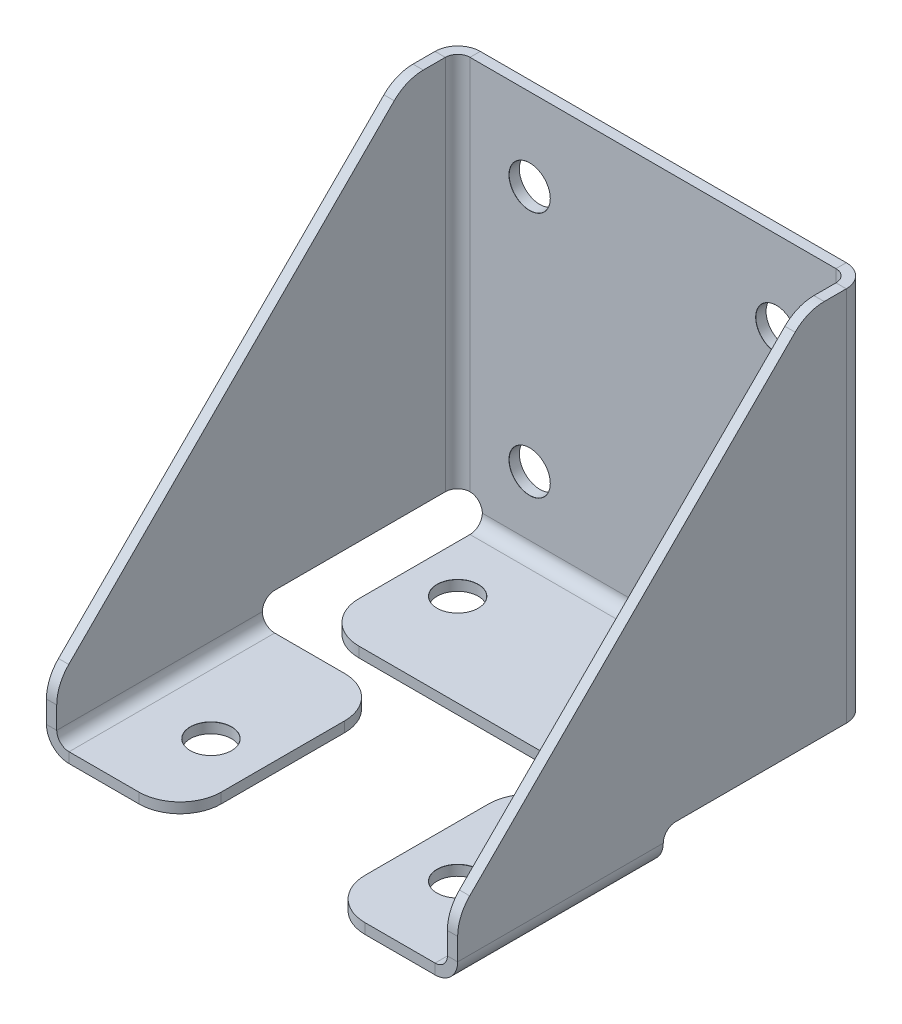
SolidWorks part; units mm, degrees
note: The reader was unsure of these and kept them because the rebuilt part matched: flange length of "Edge-Flange1", "Edge-Flange2", "Edge-Flange3".
ref_plane "Front Plane" through (0, 0, 0) normal (0, 0, 1) x (1, 0, 0)
ref_plane "Top Plane" through (0, 0, 0) normal (0, 1, 0) x (1, 0, 0)
ref_plane "Right Plane" through (0, 0, 0) normal (1, 0, 0) x (0, 0, -1)
sketch "Sketch1" plane through (0, 0, 0) normal (0, 0, 1) x (1, 0, 0)
  line L1 (50, -50) -> (-50, -50)
  line L2 (50, -50) -> (50, 50)
  line L3 (50, 50) -> (-50, 50)
  line L4 (-50, -50) -> (-50, 50)
  line L5 (50, -50) -> (-50, 50) construction
  line L6 (50, 50) -> (-50, -50) construction
  point P0 (0, 0)
  dimension "D1" = 100
  dimension "D2" = 100
base flange "Base-Flange1" sketch "Sketch1" thickness 2.5 reverse thickness direction no parameters "D1"=0.7366
edge flange "Edge-Flange1" sketch "Sketch10" flange angle 90 flange length 42.5 flange position material inside bend radius 3 thickness 2.5 relief rectangular parameters "D6"=10
sketch "Sketch10" plane through (0, -50, 0) normal (0, 1, 0) x (-1, 0, 0)
  line L0 (50, 0) -> (-50, 0) construction
  line L1 (41.5, 0) -> (-41.5, 0)
  line L2 (41.5, 0) -> (41.5, 40)
  line L3 (41.5, 40) -> (-41.5, 40)
  line L4 (-41.5, 40) -> (-41.5, 0)
  line L6 (-50, -2.5) -> (-50, 0) construction
  line L7 (50, -2.5) -> (50, 0) construction
  dimension "D1" = 8.5
  dimension "D2" = 8.5
  dimension "D3" = 40
bend "EdgeBend1" bend radius 3 bend angle 90 parameters "D5"=1
edge flange "Edge-Flange2" sketch "Sketch13" flange angle 90 flange length 100 flange position material inside bend radius 3 thickness 2.5 relief rectangular parameters "D6"=10
sketch "Sketch13" plane through (50, 0, 0) normal (1, 0, 0) x (0, 1, 0)
  line L0 (-50, 0) -> (50, 0) construction
  line L1 (-50, 0) -> (50, 0)
  line L2 (-50, 0) -> (-50, 97.5)
  line L3 (-50, 97.5) -> (50, 97.5)
  line L4 (50, 97.5) -> (50, 0)
bend "EdgeBend2" bend radius 3 bend angle 90 parameters "D5"=2
edge flange "Edge-Flange3" sketch "Sketch16" flange angle 90 flange length 32.5 flange position material inside bend radius 3 thickness 2.5 relief rectangular parameters "D6"=10
sketch "Sketch16" plane through (47.5, -50, 0) normal (0, -1, 0) x (0, 0, 1)
  line L2 (47.5, 0) -> (47.5, 30)
  line L3 (47.5, 30) -> (97.5, 30)
  line L4 (97.5, 30) -> (97.5, 0)
  line L7 (97.5, 0) -> (3, 0) construction
  line L8 (97.5, 0) -> (47.5, 0)
  line L9 (97.5, -2.5) -> (97.5, 0) construction
  dimension "D1" = 30
  dimension "D2" = 50
bend "EdgeBend3" bend radius 3 bend angle 90 parameters "D5"=3
sketch "Sketch17" plane through (50, 0, 0) normal (1, 0, 0) x (0, 0, -1)
  line L0 (-47.5, -50) -> (-47.5, -44.5) construction
  line L1 (-47.5, -41.5) -> (2.5, -41.5)
  line L2 (-47.5, -41.5) -> (-47.5, -50)
  line L3 (-47.5, -50) -> (2.5, -50)
  line L4 (2.5, -41.5) -> (2.5, -50)
  dimension "D1" = 8.5
extrude "Cut-Extrude1" cut sketch "Sketch17" against normal blind 8.5 normal cut yes
sketch "Sketch18" plane through (50, 0, 0) normal (1, 0, 0) x (0, 0, -1)
  line L0 (-97.5, 50) -> (-97.5, -35)
  line L1 (-97.5, 50) -> (-97.5, -44.5) construction
  line L2 (-97.5, -35) -> (-12.5, 50)
  line L3 (-3, 50) -> (-97.5, 50) construction
  line L4 (-12.5, 50) -> (-97.5, 50)
  line L5 (2.5, 50) -> (2.5, -41.5) construction
  dimension "D1" = 45
  dimension "D2" = 15
extrude "Cut-Extrude2" cut sketch "Sketch18" against normal up to next normal cut yes
hole_wizard "Ø10.0mm Dowel Hole1" positions "Sketch19" profile "Sketch20" hole size "Ø10.0" standard "ISO" end condition up to next
sketch "Sketch19" plane through (0, 0, 0) normal (0, 0, 1) x (1, 0, 0)
  line L0 (44.5, 50) -> (-50, 50) construction
  line L1 (44.5, -50) -> (17.5, -50) construction
  line L2 (50, -35) -> (50, 50) construction
  point P0 (30, 30)
  point P2 (30, -30)
  dimension "D1" = 20
  dimension "D2" = 20
  dimension "D3" = 20
  dimension "D4" = 20
sketch "Sketch20" plane through (30, 30, 0) normal (1, 0, 0) x (0, -1, 0)
  line L0 (0, 0) -> (0, 2.5)
  line L1 (0, 2.5) -> (5, 2.5)
  line L2 (5, 2.5) -> (5, 0.025)
  line L3 (5, 0.025) -> (5.025, 0)
  line L5 (5.025, 0) -> (0, 0)
  line L6 (-5, 0.025) -> (-5.025, 0) construction
  line L11 (0, -6.35) -> (0, 107.95) construction
  dimension "Thru Hole Dia." = 10
  dimension "Thru Hole Depth" = 2.5
  dimension "Near C'Sink Dia." = 10.05
  dimension "Near C'Sink Angle" = 90
hole_wizard "Ø10.0mm Dowel Hole2" positions "Sketch21" profile "Sketch22" hole size "Ø10.0" standard "ISO" end condition up to next
sketch "Sketch21" plane through (0, -47.5, 0) normal (0, 1, 0) x (1, 0, 0)
  line L0 (50, -97.5) -> (50, -12.5) construction
  line L1 (44.5, -97.5) -> (17.5, -97.5) construction
  line L2 (44.5, 2.5) -> (-50, 2.5) construction
  point P0 (30, -17.5)
  point P2 (30, -77.5)
  dimension "D1" = 20
  dimension "D2" = 20
  dimension "D3" = 20
  dimension "D4" = 20
sketch "Sketch22" plane through (30, -47.5, 17.5) normal (1, 0, 0) x (0, 0, 1)
  line L0 (0, 0) -> (0, 2.5)
  line L1 (0, 2.5) -> (5, 2.5)
  line L2 (5, 2.5) -> (5, 0.025)
  line L3 (5, 0.025) -> (5.025, 0)
  line L5 (5.025, 0) -> (0, 0)
  line L6 (-5, 0.025) -> (-5.025, 0) construction
  line L11 (0, -6.35) -> (0, 107.95) construction
  dimension "Thru Hole Dia." = 10
  dimension "Thru Hole Depth" = 2.5
  dimension "Near C'Sink Dia." = 10.05
  dimension "Near C'Sink Angle" = 90
mirror "Mirror3" about plane through (0, 0, 0) normal (1, 0, 0) of "Edge-Flange2", "Edge-Flange3", "Cut-Extrude1", "Cut-Extrude2", "Ø10.0mm Dowel Hole1", "Ø10.0mm Dowel Hole2"
bend "MirrorBend4" bend radius 3 bend angle 90 parameters "D5"=4
bend "MirrorBend5" bend radius 3 bend angle 90 parameters "D5"=5
fillet "Fillet3" radius 3 16 edges at (50, -43, 47.5) (47.5, -43, 47.5) (48.75, -41.5, 47.5) (41.5, -41.5, -1.25) (43, -41.5, 0) (43, -41.5, -2.5) (41.5, -43, -2.5) (41.5, -43, 0) (-41.5, -43, -2.5) (-41.5, -43, 0) (-50, -43, 47.5) (-47.5, -43, 47.5) (-48.75, -41.5, 47.5) (-43, -41.5, -2.5) (-41.5, -41.5, -1.25) (-43, -41.5, 0)
fillet "Fillet4" radius 10 10 edges at (41.5, -48.75, 40) (17.5, -48.75, 47.5) (17.5, -48.75, 97.5) (-17.5, -48.75, 47.5) (-17.5, -48.75, 97.5) (-41.5, -48.75, 40) (48.75, 50, 12.5) (48.75, -35, 97.5) (-48.75, -35, 97.5) (-48.75, 50, 12.5)
sketch "Bend-Lines1" [suppressed] plane through (0, 0, 0) normal (0, 1, 0) x (1, 0, 0)
sketch "Bounding-Box1" [suppressed] plane through (0, 0, 0) normal (0, 1, 0) x (1, 0, 0)
sheet metal parameters "Sheet-Metal1" thickness 2.5 parameters "D1"=0.7366
flat pattern "Flat-Pattern1"
sketch "Bend-Lines2" plane through (0, 0, 0) normal (0, 1, 0) x (1, 0, 0)
sketch3d "Bounding-Box2"
  line L0 (-50, 50, 0) -> (-50, -50, 0) construction
  line L1 (50, 50, 0) -> (50, -50, 0) construction
  line L2 (-50, 50, 0) -> (50, 50, 0) construction
  line L3 (-50, -50, 0) -> (50, -50, 0) construction
sheet metal parameters "Sheet-Metal2" thickness 2.5 parameters "D1"=0.7366
flat pattern "Flat-Pattern1"
sketch "Bend-Lines2" plane through (0, 0, 0) normal (0, 0, 1) x (1, 0, 0)
  line L0 (-41.5, -47.8379) -> (41.5, -47.8379) construction
  line L1 (-41.5, -47.8379) -> (41.5, -47.8379) construction
sketch3d "Bounding-Box2"
  line L0 (50, 50, 0) -> (50, -88.1759, 0) construction
  line L1 (-50, 50, 0) -> (-50, -88.1759, 0) construction
  line L2 (50, 50, 0) -> (-50, 50, 0) construction
  line L3 (50, -88.1759, 0) -> (-50, -88.1759, 0) construction
bend of the flat pattern "Flatten-<EdgeBend1>1"
sheet metal parameters "Sheet-Metal3" thickness 2.5 parameters "D1"=0.7366
flat pattern "Flat-Pattern1"
sketch "Bend-Lines2" plane through (0, 0, 0) normal (0, 0, 1) x (1, 0, 0)
  line L0 (-41.5, -47.8379) -> (41.5, -47.8379) construction
  line L1 (-41.5, -47.8379) -> (41.5, -47.8379) construction
  line L2 (47.8379, -50) -> (47.8379, 50) construction
  line L3 (47.8379, -50) -> (47.8379, 50) construction
sketch3d "Bounding-Box2"
  line L0 (-50, -88.1759, 0) -> (145.6759, -88.1759, 0) construction
  line L1 (-50, 50, 0) -> (145.6759, 50, 0) construction
  line L2 (-50, -88.1759, 0) -> (-50, 50, 0) construction
  line L3 (145.6759, -88.1759, 0) -> (145.6759, 50, 0) construction
bend of the flat pattern "Flatten-<EdgeBend1>1"
bend of the flat pattern "Flatten-<EdgeBend2>1"
sheet metal parameters "Sheet-Metal5" thickness 2.5 parameters "D1"=0.7366
flat pattern "Flat-Pattern1"
sketch "Bend-Lines2" plane through (0, 0, 0) normal (0, 0, 1) x (1, 0, 0)
  line L0 (-41.5, -47.8379) -> (41.5, -47.8379) construction
  line L1 (-41.5, -47.8379) -> (41.5, -47.8379) construction
  line L2 (47.8379, -50) -> (47.8379, 50) construction
  line L3 (47.8379, -50) -> (47.8379, 50) construction
  line L4 (95.6759, -47.8379) -> (145.6759, -47.8379) construction
  line L5 (95.6759, -47.8379) -> (145.6759, -47.8379) construction
sketch3d "Bounding-Box2"
  line L0 (-50, -88.1759, 0) -> (145.6759, -88.1759, 0) construction
  line L1 (-50, 50, 0) -> (145.6759, 50, 0) construction
  line L2 (-50, -88.1759, 0) -> (-50, 50, 0) construction
  line L3 (145.6759, -88.1759, 0) -> (145.6759, 50, 0) construction
bend of the flat pattern "Flatten-<EdgeBend1>1"
bend of the flat pattern "Flatten-<EdgeBend2>1"
bend of the flat pattern "Flatten-<EdgeBend3>1"
sheet metal parameters "Sheet-Metal6" thickness 2.5 parameters "D1"=0.7366
flat pattern "Flat-Pattern1"
sketch "Bend-Lines2" plane through (0, 0, 0) normal (0, 0, 1) x (1, 0, 0)
  line L0 (-41.5, -47.8379) -> (41.5, -47.8379) construction
  line L1 (-41.5, -47.8379) -> (41.5, -47.8379) construction
  line L2 (47.8379, -43.25) -> (47.8379, 50) construction
  line L3 (47.8379, -43.25) -> (47.8379, 50) construction
  line L4 (95.6759, -47.8379) -> (145.6759, -47.8379) construction
  line L5 (95.6759, -47.8379) -> (145.6759, -47.8379) construction
sketch3d "Bounding-Box2"
  line L0 (-50, -88.1759, 0) -> (145.6759, -88.1759, 0) construction
  line L1 (-50, 50, 0) -> (145.6759, 50, 0) construction
  line L2 (-50, -88.1759, 0) -> (-50, 50, 0) construction
  line L3 (145.6759, -88.1759, 0) -> (145.6759, 50, 0) construction
bend of the flat pattern "Flatten-<EdgeBend1>1"
bend of the flat pattern "Flatten-<EdgeBend2>1"
bend of the flat pattern "Flatten-<EdgeBend3>1"
sheet metal parameters "Sheet-Metal7" thickness 2.5 parameters "D1"=0.7366
flat pattern "Flat-Pattern1"
sketch "Bend-Lines2" plane through (0, 0, 0) normal (0, 0, 1) x (1, 0, 0)
  line L0 (-41.5, -47.8379) -> (41.5, -47.8379) construction
  line L1 (-41.5, -47.8379) -> (41.5, -47.8379) construction
  line L2 (47.8379, -43.25) -> (47.8379, 50) construction
  line L3 (47.8379, -43.25) -> (47.8379, 50) construction
  line L4 (95.6759, -47.8379) -> (145.6759, -47.8379) construction
  line L5 (95.6759, -47.8379) -> (145.6759, -47.8379) construction
sketch3d "Bounding-Box2"
  line L0 (-50, -88.1759, 0) -> (145.6759, -88.1759, 0) construction
  line L1 (-50, 50, 0) -> (145.6759, 50, 0) construction
  line L2 (-50, -88.1759, 0) -> (-50, 50, 0) construction
  line L3 (145.6759, -88.1759, 0) -> (145.6759, 50, 0) construction
bend of the flat pattern "Flatten-<EdgeBend1>1"
bend of the flat pattern "Flatten-<EdgeBend2>1"
bend of the flat pattern "Flatten-<EdgeBend3>1"
sheet metal parameters "Sheet-Metal8" thickness 2.5 parameters "D1"=0.7366
flat pattern "Flat-Pattern1"
sketch "Bend-Lines2" plane through (0, 0, 0) normal (0, 0, 1) x (1, 0, 0)
  line L0 (-41.5, -47.8379) -> (41.5, -47.8379) construction
  line L1 (-41.5, -47.8379) -> (41.5, -47.8379) construction
  line L2 (47.8379, -43.25) -> (47.8379, 50) construction
  line L3 (47.8379, -43.25) -> (47.8379, 50) construction
  line L4 (95.6759, -47.8379) -> (145.6759, -47.8379) construction
  line L5 (95.6759, -47.8379) -> (145.6759, -47.8379) construction
sketch3d "Bounding-Box2"
  line L0 (-50, -88.1759, 0) -> (145.6759, -88.1759, 0) construction
  line L1 (-50, 50, 0) -> (145.6759, 50, 0) construction
  line L2 (-50, -88.1759, 0) -> (-50, 50, 0) construction
  line L3 (145.6759, -88.1759, 0) -> (145.6759, 50, 0) construction
bend of the flat pattern "Flatten-<EdgeBend1>1"
bend of the flat pattern "Flatten-<EdgeBend2>1"
bend of the flat pattern "Flatten-<EdgeBend3>1"
sheet metal parameters "Sheet-Metal9" thickness 2.5 parameters "D1"=0.7366
flat pattern "Flat-Pattern1"
sketch "Bend-Lines2" plane through (0, 0, 0) normal (0, 0, 1) x (1, 0, 0)
  line L0 (-41.5, -47.8379) -> (41.5, -47.8379) construction
  line L1 (-41.5, -47.8379) -> (41.5, -47.8379) construction
  line L2 (47.8379, -41.5) -> (47.8379, 50) construction
  line L3 (47.8379, -41.5) -> (47.8379, 50) construction
  line L4 (95.6759, -47.8379) -> (145.6759, -47.8379) construction
  line L5 (95.6759, -47.8379) -> (145.6759, -47.8379) construction
sketch3d "Bounding-Box2"
  line L0 (-50, -88.1759, 0) -> (145.6759, -88.1759, 0) construction
  line L1 (-50, 50, 0) -> (145.6759, 50, 0) construction
  line L2 (-50, -88.1759, 0) -> (-50, 50, 0) construction
  line L3 (145.6759, -88.1759, 0) -> (145.6759, 50, 0) construction
bend of the flat pattern "Flatten-<EdgeBend1>1"
bend of the flat pattern "Flatten-<EdgeBend2>1"
bend of the flat pattern "Flatten-<EdgeBend3>1"
sheet metal parameters "Sheet-Metal10" thickness 2.5 parameters "D1"=0.7366
flat pattern "Flat-Pattern1"
sketch "Bend-Lines2" plane through (0, 0, 0) normal (0, 0, 1) x (1, 0, 0)
  line L0 (-41.5, -47.8379) -> (41.5, -47.8379) construction
  line L1 (-41.5, -47.8379) -> (41.5, -47.8379) construction
  line L2 (47.8379, -41.5) -> (47.8379, 50) construction
  line L3 (47.8379, -41.5) -> (47.8379, 50) construction
  line L4 (95.6759, -47.8379) -> (145.6759, -47.8379) construction
  line L5 (95.6759, -47.8379) -> (145.6759, -47.8379) construction
  line L6 (-145.6759, -47.8379) -> (-95.6759, -47.8379) construction
  line L7 (-47.8379, 50) -> (-47.8379, -41.5) construction
  line L8 (-145.6759, -47.8379) -> (-95.6759, -47.8379) construction
  line L9 (-47.8379, 50) -> (-47.8379, -41.5) construction
sketch3d "Bounding-Box2" [suppressed]
  line L0 (-145.6759, -88.1759, 0) -> (145.6759, -88.1759, 0) construction
  line L1 (-145.6759, 50, 0) -> (145.6759, 50, 0) construction
  line L2 (-145.6759, -88.1759, 0) -> (-145.6759, 50, 0) construction
  line L3 (145.6759, -88.1759, 0) -> (145.6759, 50, 0) construction
bend of the flat pattern "Flatten-<EdgeBend2>1"
bend of the flat pattern "Flatten-<EdgeBend3>1"
bend of the flat pattern "Flatten-<MirrorBend4>1"
bend of the flat pattern "Flatten-<MirrorBend5>1"
bend of the flat pattern "Flatten-<EdgeBend1>1"
